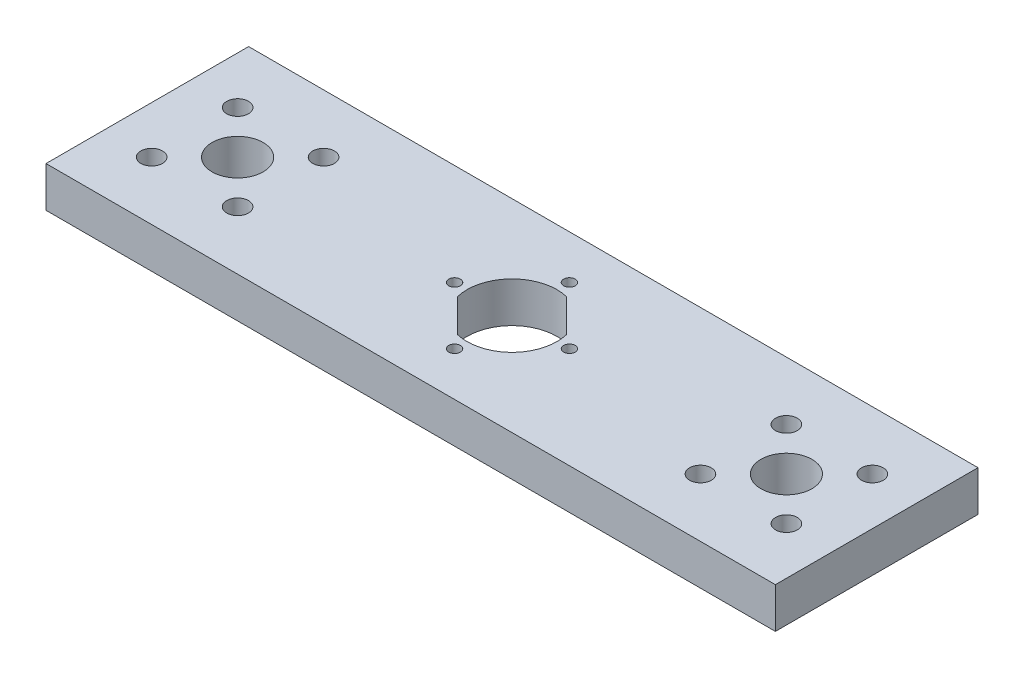
SolidWorks part; units mm, degrees
ref_plane "Front Plane" through (0, 0, 0) normal (0, 0, 1) x (1, 0, 0)
ref_plane "Top Plane" through (0, 0, 0) normal (0, 1, 0) x (1, 0, 0)
ref_plane "Right Plane" through (0, 0, 0) normal (1, 0, 0) x (0, 0, -1)
sketch "Sketch2" plane through (0, 0, 0) normal (0, 1, 0) x (1, 0, 0)
  line L0 (6.7979, 1.7581) -> (1.7581, 6.7979)
  line L1 (-57.15, -15.875) -> (57.15, -15.875)
  line L2 (-57.15, -15.875) -> (-57.15, 15.875)
  line L3 (-57.15, 15.875) -> (57.15, 15.875)
  line L4 (57.15, -15.875) -> (57.15, 15.875)
  line L5 (-57.15, -15.875) -> (57.15, 15.875) construction
  line L6 (-57.15, 15.875) -> (57.15, -15.875) construction
  line L7 (-6.7979, -1.7581) -> (-1.7581, -6.7979)
  line L16 (0, 9) -> (0, -9) construction
  line L17 (-9, 0) -> (9, 0) construction
  line L18 (-57.15, 0) -> (57.15, 0) construction
  line L19 (0, 15.875) -> (0, -15.875)
  line L20 (-43, 0) -> (-36.2648, 6.7352) construction
  line L21 (-43, 0) -> (-43, 15.875) construction
  line L22 (-43, 0) -> (-49.7352, 6.7352) construction
  line L23 (-43, 0) -> (-36.2648, -6.7352) construction
  line L24 (-43, 0) -> (-49.7352, -6.7352) construction
  line L25 (43, 0) -> (49.7352, -6.7352) construction
  line L26 (43, 0) -> (36.2648, -6.7352) construction
  line L27 (43, 0) -> (36.2648, 6.7352) construction
  line L28 (43, 0) -> (49.7352, 6.7352) construction
  arc A8 (6.8508, 1.6639) -> (6.7979, 1.7581) centre (6.6565, 1.6167) ccw
  arc A9 (1.7581, 6.7979) -> (1.6639, 6.8508) centre (1.6167, 6.6565) ccw
  arc A10 (-6.8508, -1.6639) -> (-6.7979, -1.7581) centre (-6.6565, -1.6167) ccw
  arc A11 (1.6639, 6.8508) -> (-6.8508, -1.6639) centre (0, 0) ccw
  arc A12 (-1.7581, -6.7979) -> (-1.6639, -6.8508) centre (-1.6167, -6.6565) ccw
  arc A13 (-1.6639, -6.8508) -> (6.8508, 1.6639) centre (0, 0) ccw
  circle A14 centre (-9, 0) radius 0.9115
  circle A15 centre (0, -9) radius 0.9115
  circle A16 centre (9, 0) radius 0.9115
  circle A17 centre (0, 9) radius 0.9115
  circle A22 centre (-43, 0) radius 4
  circle A23 centre (43, 0) radius 4
  circle A24 centre (-36.2648, 6.7352) radius 1.7
  circle A25 centre (-49.7352, 6.7352) radius 1.7
  circle A26 centre (-36.2648, -6.7352) radius 1.7
  circle A27 centre (-49.7352, -6.7352) radius 1.7
  circle A28 centre (49.7352, -6.7352) radius 1.7
  circle A29 centre (36.2648, -6.7352) radius 1.7
  circle A30 centre (36.2648, 6.7352) radius 1.7
  circle A31 centre (49.7352, 6.7352) radius 1.7
  point P0 (0, 0)
  dimension "D5" = 1.823
  dimension "D6" = 1.823
  dimension "D7" = 1.823
  dimension "D8" = 1.823
  dimension "D9" = 8
  dimension "D10" = 8
  dimension "D13" = 3.4
  dimension "D1" = 114.3
  dimension "D2" = 31.75
  dimension "D3" = 18
  dimension "D4" = 18
  dimension "D11" = 43
  dimension "D12" = 43
  dimension "D14" = 9.525
  dimension "D15" = 45
  dimension "D16" = 9.525
extrude "Boss-Extrude1" add sketch "Sketch2" along normal blind 6.35 contours A17 L19 L3 L2 L1 A15 A13 A12 L7 A10 A11 A27 A25 A24 A22 A14 A26 | A17 L19 A11 A9 L0 A8 A13 A15 L1 L4 L3 A31 A28 A23 A16 A29 A30 region at (29.0329, 0, -0.0136) region at (-29.0329, 0, 0.0136)
equation "\"Motor Center Dist\"= 43mm"
equation "\"D12@Sketch2\"=\"Motor Center Dist\""
equation "\"D11@Sketch2\"=\"Motor Center Dist\""
